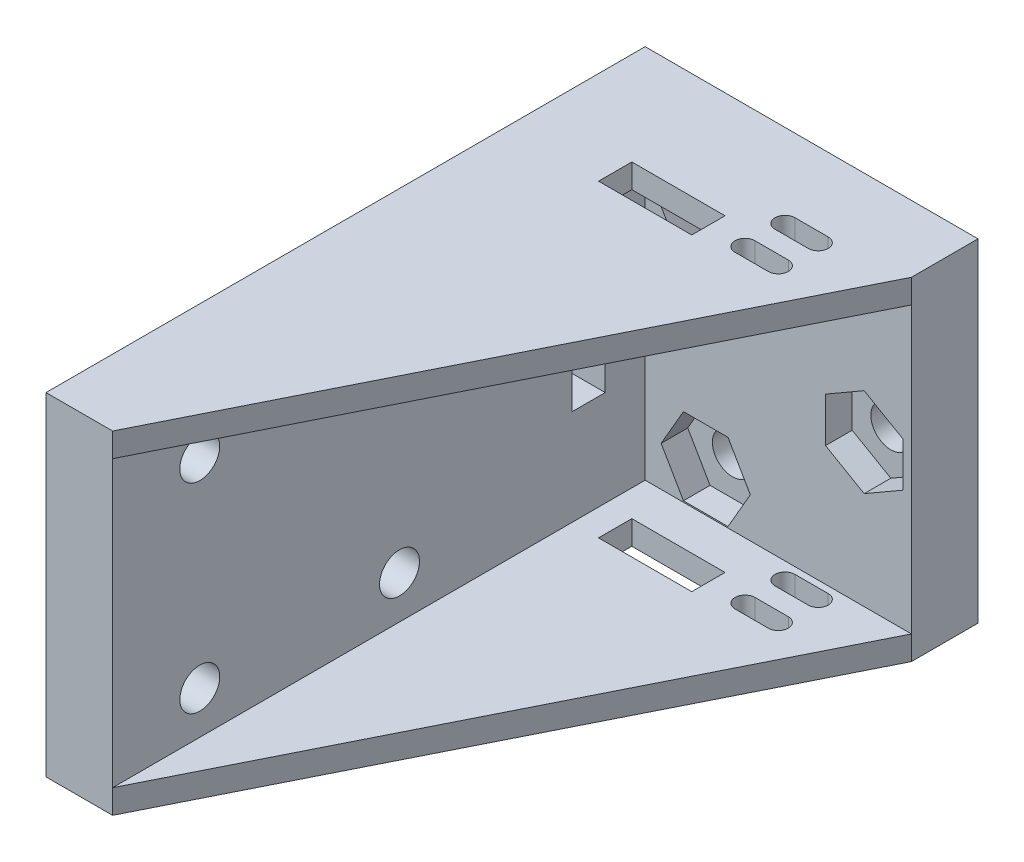
SolidWorks part; units mm, degrees
ref_plane "Front Plane" through (0, 0, 0) normal (0, 0, 1) x (1, 0, 0)
ref_plane "Top Plane" through (0, 0, 0) normal (0, 1, 0) x (1, 0, 0)
ref_plane "Right Plane" through (0, 0, 0) normal (1, 0, 0) x (0, 0, -1)
sketch "Sketch1" plane through (0, 0, 0) normal (0, 0, 1) x (1, 0, 0)
  line L1 (-45.175, -12.5) -> (-20.175, -12.5)
  line L2 (-45.175, -12.5) -> (-45.175, 12.5)
  line L3 (-45.175, 12.5) -> (-20.175, 12.5)
  line L4 (-20.175, -12.5) -> (-20.175, 12.5)
  line L5 (-45.175, -12.5) -> (-20.175, 12.5) construction
  line L6 (-45.175, 12.5) -> (-20.175, -12.5) construction
  circle A0 centre (-35.625, 7.7) radius 1.5 construction
  circle A1 centre (-35.625, 7.7) radius 1.5
  circle A2 centre (-35.625, -7.7) radius 1.5 construction
  circle A3 centre (-35.625, -7.7) radius 1.5
  circle A4 centre (-23.725, 0) radius 1.5 construction
  circle A5 centre (-23.725, 0) radius 1.5
  point P0 (-32.675, 0)
  dimension "D1" = 25
extrude "Boss-Extrude1" add sketch "Sketch1" along normal blind 5
sketch "Sketch2" plane through (0, 0, 5) normal (0, 0, 1) x (1, 0, 0)
  line L0 (-45.175, -12.5) -> (-20.175, -12.5) construction
  line L1 (-45.175, 12.5) -> (-40.175, 12.5)
  line L2 (-45.175, 12.5) -> (-45.175, -12.5)
  line L3 (-45.175, -12.5) -> (-40.175, -12.5)
  line L4 (-40.175, 12.5) -> (-40.175, -12.5)
  dimension "D1" = 5
extrude "Boss-Extrude2" add sketch "Sketch2" along normal blind 40
sketch "Sketch3" plane through (0, 0, 5) normal (0, 0, 1) x (1, 0, 0)
  line L0 (-20.175, 12.5) -> (-40.175, 12.5) construction
  line L1 (-37.2993, 4.8) -> (-33.9507, 4.8)
  line L2 (-33.9507, 4.8) -> (-32.2764, 7.7)
  line L3 (-32.2764, 7.7) -> (-33.9507, 10.6)
  line L4 (-33.9507, 10.6) -> (-37.2993, 10.6)
  line L5 (-37.2993, 10.6) -> (-38.9736, 7.7)
  line L6 (-38.9736, 7.7) -> (-37.2993, 4.8)
  line L7 (-33.9507, -4.8) -> (-37.2993, -4.8)
  line L8 (-37.2993, -4.8) -> (-38.9736, -7.7)
  line L9 (-38.9736, -7.7) -> (-37.2993, -10.6)
  line L10 (-37.2993, -10.6) -> (-33.9507, -10.6)
  line L11 (-33.9507, -10.6) -> (-32.2764, -7.7)
  line L12 (-32.2764, -7.7) -> (-33.9507, -4.8)
  line L13 (-23.725, -3.3486) -> (-20.825, -1.6743)
  line L14 (-20.825, -1.6743) -> (-20.825, 1.6743)
  line L15 (-20.825, 1.6743) -> (-23.725, 3.3486)
  line L16 (-23.725, 3.3486) -> (-26.625, 1.6743)
  line L17 (-26.625, 1.6743) -> (-26.625, -1.6743)
  line L18 (-26.625, -1.6743) -> (-23.725, -3.3486)
  line L19 (-20.175, -12.5) -> (-20.175, 12.5) construction
  circle A0 centre (-35.625, 7.7) radius 2.9 construction
  circle A1 centre (-35.625, -7.7) radius 2.9 construction
  circle A2 centre (-23.725, 0) radius 2.9 construction
  dimension "D1" = 5.8
extrude "Cut-Extrude1" cut sketch "Sketch3" against normal blind 2
sketch "Sketch4" plane through (0, -12.5, 0) normal (0, -1, 0) x (1, 0, 0)
  line L0 (-40.175, 45) -> (-20.175, 5)
  line L1 (-20.175, 5) -> (-40.175, 5)
  line L2 (-40.175, 5) -> (-40.175, 45)
extrude "Boss-Extrude3" add sketch "Sketch4" against normal blind 1.8
sketch "Sketch5" plane through (0, 12.5, 0) normal (0, 1, 0) x (1, 0, 0)
  line L3 (-40.175, -45) -> (-20.175, -5)
  line L4 (-20.175, -5) -> (-40.175, -5)
  line L5 (-40.175, -5) -> (-40.175, -45)
  line L6 (-40.175, -45) -> (-20.175, -5)
  line L7 (-20.175, -5) -> (-40.175, -5)
  line L8 (-40.175, -5) -> (-40.175, -45)
  dimension "D1" = 0
extrude "Boss-Extrude4" add sketch "Sketch5" against normal blind 1.8
sketch "Sketch6" plane through (0, 12.5, 0) normal (0, 1, 0) x (1, 0, 0)
  line L0 (-40.175, -5) -> (-20.175, -5) construction
  line L1 (-40.175, -5) -> (-20.175, -5)
  line L3 (-38.175, -8) -> (-31.175, -8)
  line L4 (-38.175, -8) -> (-38.175, -10.5)
  line L5 (-38.175, -10.5) -> (-31.175, -10.5)
  line L6 (-31.175, -8) -> (-31.175, -10.5)
  dimension "D1" = 7
  dimension "D2" = 2.5
  dimension "D3" = 2
  dimension "D4" = 3
extrude "Cut-Extrude2" cut sketch "Sketch6" against normal through all contours L6 L3 L4 L5 region at (-34.675, 12.5, 9.25)
sketch "Sketch7" plane through (-40.175, 0, 0) normal (1, 0, 0) x (0, 0, -1)
  line L0 (-10.5, 10.7) -> (-8, 10.7) construction
  line L1 (-10.5, 10.7) -> (-8, 10.7) construction
  line L2 (-45, 0) -> (-10.5, 0) construction
  line L3 (-10.5, 3.5) -> (-8, 3.5)
  line L4 (-10.5, 3.5) -> (-10.5, -3.5)
  line L5 (-10.5, -3.5) -> (-8, -3.5)
  line L6 (-8, 3.5) -> (-8, -3.5)
  line L7 (-45, -10.7) -> (-45, 10.7) construction
  line L8 (-10.5, 3.5) -> (-10.5, 10.7) construction
  dimension "D1" = 7
  dimension "D2" = 2.5
extrude "Cut-Extrude3" cut sketch "Sketch7" against normal through all
sketch "Sketch8" plane through (0, -12.5, 0) normal (0, -1, 0) x (1, 0, 0)
  line L0 (-20.175, 5) -> (-40.175, 5) construction
  line L1 (-20.175, 5) -> (-40.175, 5)
  line L2 (-27.175, 5) -> (-27.175, 25.3759) construction
  line L3 (-28.425, 6.25) -> (-25.925, 6.25) construction
  line L4 (-28.425, 7) -> (-25.925, 7)
  line L5 (-28.425, 5.5) -> (-25.925, 5.5)
  line L6 (-25.925, 9.25) -> (-28.425, 9.25) construction
  line L7 (-25.925, 8.5) -> (-28.425, 8.5)
  line L8 (-25.925, 10) -> (-28.425, 10)
  line L9 (-31.175, 8) -> (-31.175, 10.5) construction
  arc A0 (-28.425, 7) -> (-28.425, 5.5) centre (-28.425, 6.25) ccw
  arc A1 (-25.925, 5.5) -> (-25.925, 7) centre (-25.925, 6.25) ccw
  arc A2 (-25.925, 8.5) -> (-25.925, 10) centre (-25.925, 9.25) ccw
  arc A3 (-28.425, 10) -> (-28.425, 8.5) centre (-28.425, 9.25) ccw
  point P6 (-27.175, 6.25)
  point P12 (-27.175, 9.25)
  dimension "D1" = 4
  dimension "D2" = 0.5
  dimension "D3" = 1.5
  dimension "D4" = 3
  dimension "D5" = 4
extrude "Cut-Extrude4" cut sketch "Sketch8" against normal through all contours L8 A3 L7 A2 | L5 A1 L4 A0 region at (-27.175, -12.5, 6.25) region at (-27.175, -12.5, 9.25)
sketch "Sketch9" plane through (-45.175, 0, 0) normal (-1, 0, 0) x (0, 0, 1)
  line L0 (18.45, 23.7845) -> (18.45, -33.9363) construction
  line L1 (15.45, -13.4) -> (15.45, 13.4) construction
  line L2 (21.95, 23.7845) -> (21.95, -22.2084) construction
  line L3 (21.95, 7.5) -> (49.7465, 7.5) construction
  line L5 (21.95, -7.5) -> (49.4161, -7.5) construction
  line L6 (45, 12.5) -> (0, 12.5) construction
  line L7 (45, -12.5) -> (0, -12.5) construction
  circle A0 centre (23.45, 7.5) radius 1.5
  circle A1 centre (23.45, -7.5) radius 1.5
  circle A2 centre (38.45, 7.5) radius 1.5
  circle A3 centre (38.45, -7.5) radius 1.5
  dimension "D3" = 3
  dimension "D1" = 3
  dimension "D2" = 3.5
  dimension "D4" = 5
  dimension "D5" = 15
  dimension "D6" = 5
  dimension "D7" = 15
extrude "Cut-Extrude5" cut sketch "Sketch9" against normal through all
